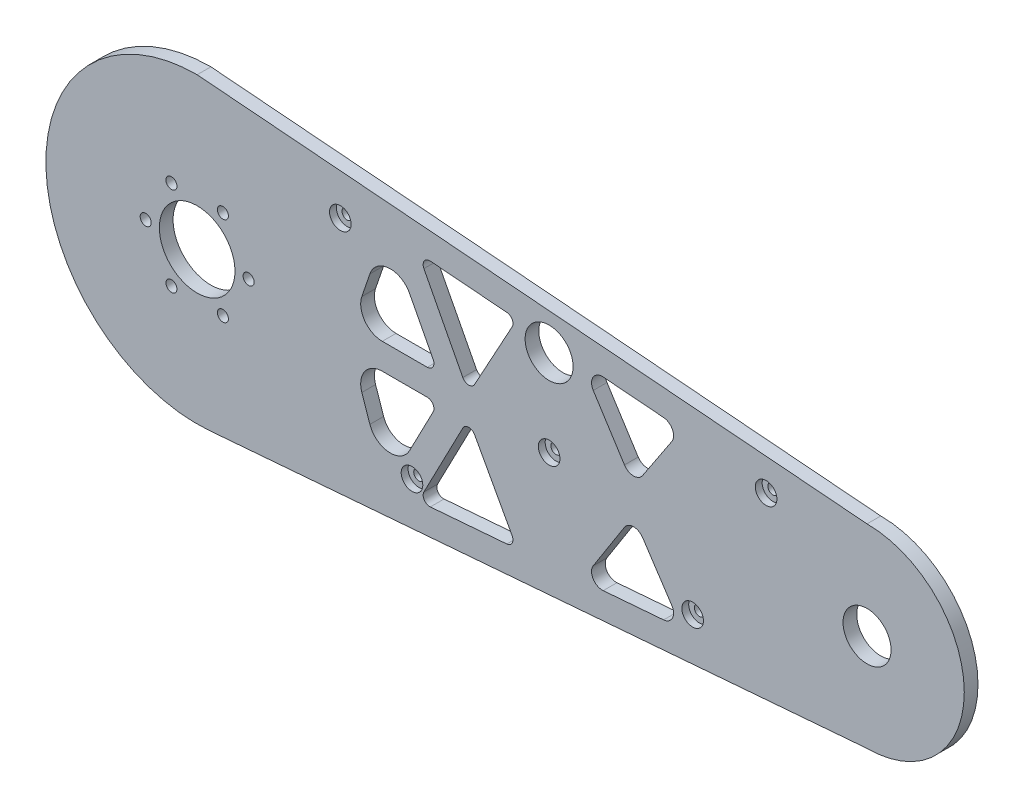
SolidWorks part; units mm, degrees
other "Marca1"
sketch "Croquis3" plane through (-70, -70, 6.35) normal (0, 0, 1) x (1, 0, 0)
material "6061-O (SS)"
ref_plane "Front Plane" through (0, 0, 0) normal (0, 0, 1) x (1, 0, 0)
ref_plane "Top Plane" through (0, 0, 0) normal (0, 1, 0) x (1, 0, 0)
ref_plane "Right Plane" through (0, 0, 0) normal (1, 0, 0) x (0, 0, -1)
sketch "Sketch1" plane through (0, 0, 0) normal (0, 0, 1) x (1, 0, 0)
  line L0 (0, 70) -> (310, 45)
  line L1 (5.1714, -69.8087) -> (310, -45)
  line L2 (0, 0) -> (310, 0) construction
  line L3 (107.899, 49.2595) -> (143.3142, 46.4034)
  line L4 (76.2798, 6) -> (106.4818, 6)
  line L5 (219.6238, 32.8105) -> (206.1309, 12.4175)
  line L6 (197.7459, 12.4871) -> (183.2969, 35.1335)
  line L7 (162.8785, 6) -> (162.8785, -6) construction
  line L8 (258.6323, 64.5867) -> (258.6323, 39.5867) construction
  line L9 (145.7701, 41.8523) -> (128.3786, 10.0664)
  line L10 (122.9411, 10.1232) -> (104.9173, 44.7652)
  line L11 (102.346, 49.7073) -> (42.0027, 49.7073) construction
  line L12 (187.9139, 42.8067) -> (215.8558, 40.5533)
  line L13 (162.8785, 44.8257) -> (162.8785, 6) construction
  line L14 (67.1248, 64.5867) -> (162.8785, 40) construction
  line L15 (201.8849, 6) -> (201.8849, 41.68) construction
  line L16 (125.6066, 5) -> (125.6066, 47.8315) construction
  line L17 (98.2753, 31.5321) -> (109.2158, 10.5043)
  line L18 (125.6066, -5) -> (125.6066, -47.8315) construction
  line L19 (201.8849, -6) -> (201.8849, -41.68) construction
  line L20 (162.8785, -44.8257) -> (162.8785, -6) construction
  line L21 (102.346, -49.7073) -> (42.0027, -49.7073) construction
  line L22 (98.2753, -31.5321) -> (109.2158, -10.5043)
  line L23 (67.1248, 64.5867) -> (409.6974, 64.5867) construction
  line L24 (187.9139, -42.8067) -> (215.8558, -40.5533)
  line L25 (122.9411, -10.1232) -> (104.9173, -44.7652)
  line L26 (145.7701, -41.8523) -> (128.3786, -10.0664)
  line L27 (162.8785, 0) -> (258.6323, 64.5867) construction
  line L28 (67.1248, 64.5867) -> (67.1248, 39.5867) construction
  line L29 (197.7459, -12.4871) -> (183.2969, -35.1335)
  line L30 (219.6238, -32.8105) -> (206.1309, -12.4175)
  line L31 (76.2798, -6) -> (106.4818, -6)
  line L32 (107.899, -49.2595) -> (143.3142, -46.4034)
  line L33 (0, -6.35) -> (0, 6.35) construction
  line L34 (67.1248, 39.5867) -> (162.8785, 40) construction
  line L35 (162.8785, 40) -> (68.3705, 24.1395) construction
  line L36 (79.9417, 30.1512) -> (72.3419, 7.919)
  line L37 (79.9417, -30.1512) -> (72.3419, -7.919)
  arc A0 (72.3419, 7.919) -> (76.2798, 6) centre (76.2798, 11) ccw
  arc A1 (310, -45) -> (310, 45) centre (310, 0) ccw
  circle A2 centre (0, 0) radius 14.2938
  circle A3 centre (310, 0) radius 11.115
  arc A4 (79.9417, 30.1512) -> (98.2753, 31.5321) centre (89.4042, 26.9165) cw
  arc A5 (98.2753, -31.5321) -> (79.9417, -30.1512) centre (89.4042, -26.9165) cw
  arc A6 (0, 70) -> (5.1714, -69.8087) centre (0, 0) ccw
  arc A7 (187.9139, 42.8067) -> (183.2969, 35.1335) centre (187.512, 37.8229) ccw
  arc A8 (219.6238, 32.8105) -> (215.8558, 40.5533) centre (215.4539, 35.5695) ccw
  arc A9 (206.1309, 12.4175) -> (197.7459, 12.4871) centre (201.961, 15.1765) cw
  circle A10 centre (162.8785, 40) radius 11.1125
  arc A13 (106.4818, 6) -> (109.2158, 10.5043) centre (106.4818, 9.0819) ccw
  arc A14 (122.9411, 10.1232) -> (128.3786, 10.0664) centre (125.675, 11.5456) ccw
  arc A15 (145.7701, 41.8523) -> (143.3142, 46.4034) centre (143.0665, 43.3316) ccw
  arc A16 (107.899, 49.2595) -> (104.9173, 44.7652) centre (107.6512, 46.1876) ccw
  arc A17 (107.899, -49.2595) -> (104.9173, -44.7652) centre (107.6512, -46.1876) cw
  arc A18 (145.7701, -41.8523) -> (143.3142, -46.4034) centre (143.0665, -43.3316) cw
  arc A19 (122.9411, -10.1232) -> (128.3786, -10.0664) centre (125.675, -11.5456) cw
  arc A20 (106.4818, -6) -> (109.2158, -10.5043) centre (106.4818, -9.0819) cw
  arc A24 (206.1309, -12.4175) -> (197.7459, -12.4871) centre (201.961, -15.1765) ccw
  arc A25 (219.6238, -32.8105) -> (215.8558, -40.5533) centre (215.4539, -35.5695) cw
  arc A26 (187.9139, -42.8067) -> (183.2969, -35.1335) centre (187.512, -37.8229) cw
  arc A29 (72.3419, -7.919) -> (76.2798, -6) centre (76.2798, -11) cw
  point P31 (177.8851, 43.6155)
  point P42 (187.6504, 6)
  point P44 (87.496, 52.25)
  point P45 (138.1067, 6)
  point P79 (87.496, -52.25)
  point P100 (138.1067, -6)
  point P101 (187.6504, -6)
  point P102 (177.8851, -43.6155)
  point P104 (0, 0)
  point P114 (310, 0)
  point P119 (0.2114, 0.3175)
  dimension "D2" = 45
  dimension "D3" = 12.7
  dimension "D4" = 22.23
  dimension "D6" = 12
  dimension "D11" = 5
  dimension "D12" = 70
  dimension "D13" = 25
  dimension "D8" = 5
  dimension "D14" = 12
  dimension "D15" = 25
  dimension "D16" = 310
  dimension "D17" = 22.225
  dimension "D5" = 28.5877
  dimension "D19" = 10
  dimension "D20" = 10
  dimension "D7" = 6
  dimension "D9" = 9.279
  dimension "D10" = 34
  dimension "D18" = 40
extrude "Boss-Extrude1" add sketch "Sketch1" along normal blind 6.35
sketch "Sketch2" plane through (0, 0, 6.35) normal (0, 0, 1) x (1, 0, 0)
  line L0 (263.0927, 39.4927) -> (-0.4655, 64.9983)
  line L1 (4.6885, -64.8307) -> (263.1366, -39.5384)
  arc A0 (-0.4655, 64.9983) -> (4.6885, -64.8307) centre (0, 0) ccw
  arc A1 (263.1366, -39.5384) -> (270.3186, -23.7999) centre (262.1626, -29.5859) ccw
  circle A2 centre (0, 0) radius 40
  arc A3 (270.292, 23.7623) -> (270.3186, -23.7999) centre (303.867, 0) ccw
  arc A4 (270.292, 23.7623) -> (263.0927, 39.4927) centre (262.1295, 29.5392) ccw
  dimension "D1" = 10
  dimension "D2" = 41.133
  dimension "D3" = 65
ref_plane "Plane1" through (0, 0, 10) normal (0, 0, 1) x (1, 0, 0)
sketch "Croquis1" plane through (0, 0, 6.35) normal (0, 0, 1) x (1, 0, 0)
  line L0 (5.1714, -69.8087) -> (310, -45) construction
  line L1 (99.4174, -42.273) -> (229.2992, -31.7024) construction
  line L9 (101.8111, -24.7362) -> (88.7465, -42.3671) construction
  line L10 (98.2753, -31.5321) -> (109.2158, -10.5043) construction
  circle A1 centre (99.4174, -42.273) radius 2.3813
  circle A2 centre (229.2992, -31.7024) radius 2.3813
  point P20 (0, 0)
  dimension "D5" = 4.7625
  dimension "D1" = 4.7625
  dimension "D2" = 19.8
extrude "Cortar-Extruir1" cut sketch "Croquis1" against normal blind 50
sketch "Croquis2" plane through (0, 0, 6.35) normal (0, 0, 1) x (1, 0, 0)
  line L0 (99.4174, -42.273) -> (229.2992, -31.7024) construction
  circle A0 centre (99.4174, -42.273) radius 5
  circle A1 centre (229.2992, -31.7024) radius 5
  dimension "D1" = 10
extrude "Cortar-Extruir2" cut sketch "Croquis2" against normal blind 3.175
sketch "Croquis4" plane through (0, 0, 6.35) normal (0, 0, 1) x (1, 0, 0)
  line L0 (162.8785, 40) -> (162.8785, -40) construction
  line L1 (135.7539, -40) -> (190.0032, -40) construction
  circle A0 centre (162.8785, 0) radius 5
  point P8 (162.8785, -40)
  dimension "D1" = 10
  dimension "D2" = 40
extrude "Cortar-Extruir3" cut sketch "Croquis4" against normal blind 3.175
sketch "Croquis5" plane through (0, 0, 6.35) normal (0, 0, 1) x (1, 0, 0)
  circle A0 centre (162.8785, 0) radius 2.3813
  dimension "D1" = 4.7625
extrude "Cortar-Extruir5" cut sketch "Croquis5" against normal blind 10
sketch "Croquis6" plane through (0, 0, 6.35) normal (0, 0, 1) x (1, 0, 0)
  line L0 (99.4174, -42.273) -> (229.2992, -31.7024) construction
  line L1 (229.2992, -31.7024) -> (263.2934, 34.0273) construction
  line L2 (99.4174, -42.273) -> (66.2632, 45.6861) construction
  circle A0 centre (66.2632, 45.6861) radius 2.3813
  circle A1 centre (263.2934, 34.0273) radius 2.3813
  dimension "D5" = 4.7625
  dimension "D1" = 94
  dimension "D2" = 74
  dimension "D3" = 106
  dimension "D4" = 238
extrude "Cortar-Extruir6" cut sketch "Croquis6" against normal blind 10
sketch "Croquis7" plane through (0, 0, 6.35) normal (0, 0, 1) x (1, 0, 0)
  circle A0 centre (66.2632, 45.6861) radius 5
  circle A1 centre (263.2934, 34.0273) radius 5
  dimension "D1" = 10
extrude "Cortar-Extruir7" cut sketch "Croquis7" against normal blind 3.17
sketch "Croquis8" plane through (0, 0, 6.35) normal (0, 0, 1) x (1, 0, 0)
  circle A0 centre (0, 0) radius 17.5
  dimension "D1" = 35
extrude "Cortar-Extruir8" cut sketch "Croquis8" against normal blind 10
sketch "Croquis9" plane through (0, 0, 0) normal (0, 0, -1) x (-1, 0, 0)
  line L0 (0, 0) -> (23.8125, 0) construction
  circle A0 centre (0, 0) radius 23.8125 construction
  circle A1 centre (23.8125, 0) radius 2.5527
  circle A2 centre (11.9062, -20.6222) radius 2.5527
  circle A3 centre (-11.9063, -20.6222) radius 2.5527
  circle A4 centre (-23.8125, 0) radius 2.5527
  circle A5 centre (-11.9062, 20.6222) radius 2.5527
  circle A6 centre (11.9063, 20.6222) radius 2.5527
  point P17 (0, 0)
  dimension "D1" = 47.625
  dimension "D2" = 5.1054
  dimension "D3" = 6
extrude "Cortar-Extruir9" cut sketch "Croquis9" against normal blind 10
fillet "Redondeo1" radius 10 1 edges at (72.3419, -7.919, 3.175)
fillet "Redondeo2" radius 10 1 edges at (72.3419, 7.919, 3.175)
